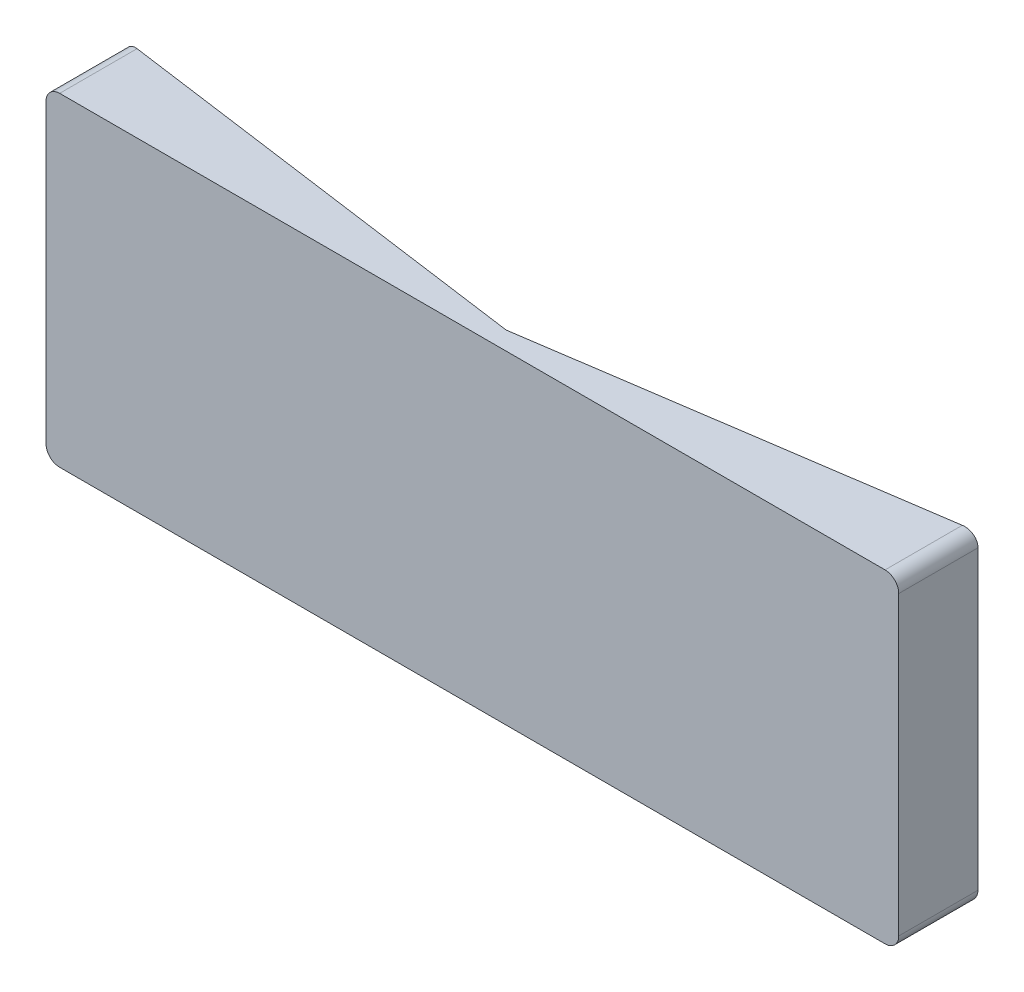
SolidWorks part; units mm, degrees
ref_plane "Front Plane" through (0, 0, 0) normal (0, 0, 1) x (1, 0, 0)
ref_plane "Top Plane" through (0, 0, 0) normal (0, 1, 0) x (1, 0, 0)
ref_plane "Right Plane" through (0, 0, 0) normal (1, 0, 0) x (0, 0, -1)
sketch "Sketch1" plane through (0, 0, 0) normal (0, 0, 1) x (1, 0, 0)
  line L0 (-79.5963, 0) -> (73.8197, 0)
  line L1 (-82.1363, -2.54) -> (-82.1363, -57.658)
  line L2 (-79.5963, -60.198) -> (73.8197, -60.198)
  line L3 (76.3597, -57.658) -> (76.3597, -2.54)
  arc A0 (76.3597, -2.54) -> (73.8197, 0) centre (73.8197, -2.54) ccw
  arc A1 (-82.1363, -57.658) -> (-79.5963, -60.198) centre (-79.5963, -57.658) ccw
  arc A2 (-79.5963, 0) -> (-82.1363, -2.54) centre (-79.5963, -2.54) ccw
  arc A3 (73.8197, -60.198) -> (76.3597, -57.658) centre (73.8197, -57.658) ccw
  point P7 (76.3597, 0)
  point P10 (-82.1363, -60.198)
  point P13 (-82.1363, 0)
  dimension "D3" = 2.54
  dimension "D4" = 2.54
  dimension "D1" = 158.496
  dimension "D2" = 60.198
extrude "Boss-Extrude1" add sketch "Sketch1" along normal blind 14.732
shell "Shell1" thickness 2.54 removed face at (-2.8883, -30.099, 0)
sketch "Sketch3" plane through (0, 0, 0) normal (0, 1, 0) x (1, 0, 0)
  line L3 (76.3597, 0) -> (0, -11.3395)
  line L4 (0, -11.3395) -> (-82.1363, 0)
  line L5 (-82.1363, 0) -> (76.3597, 0)
  line L6 (76.3597, 0) -> (0, -11.3395) construction
  line L7 (0, -11.3395) -> (-82.1363, 0) construction
extrude "Cut-Extrude1" cut sketch "Sketch3" against normal through all both and the other way through all contours L4 L5 L3
